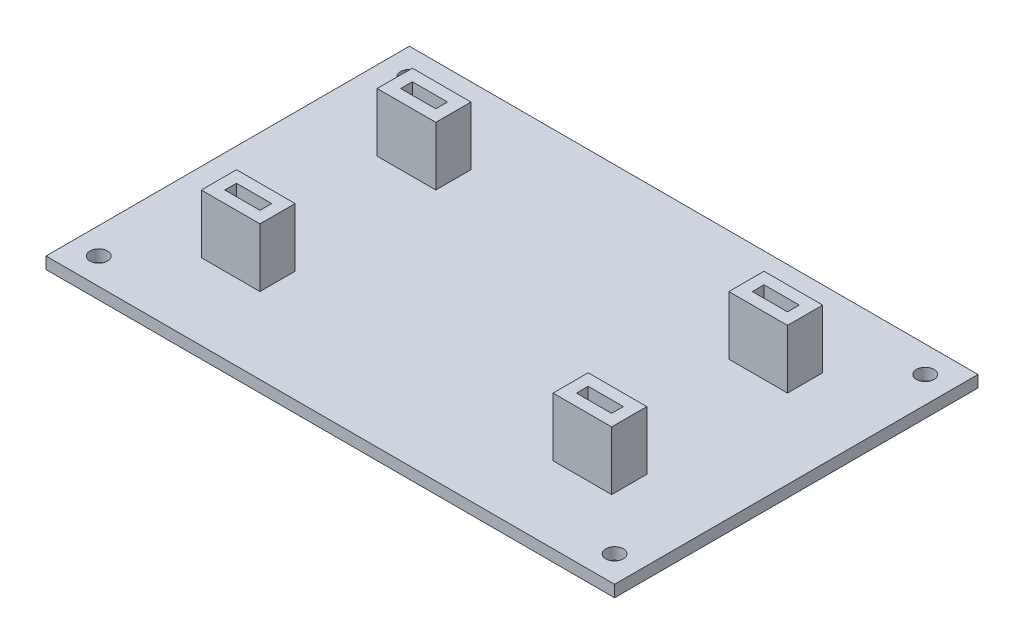
SolidWorks part; units mm, degrees
ref_plane "前视基准面" through (0, 0, 0) normal (0, 0, 1) x (1, 0, 0)
ref_plane "上视基准面" through (0, 0, 0) normal (0, 1, 0) x (1, 0, 0)
ref_plane "右视基准面" through (0, 0, 0) normal (1, 0, 0) x (0, 0, -1)
sketch "草图1" plane through (0, 0, 0) normal (0, 1, 0) x (1, 0, 0)
  line L1 (-48.5, 31) -> (48.5, 31)
  line L2 (-48.5, 31) -> (-48.5, -31)
  line L3 (-48.5, -31) -> (48.5, -31)
  line L4 (48.5, 31) -> (48.5, -31)
  line L5 (-48.5, 31) -> (48.5, -31) construction
  line L6 (-48.5, -31) -> (48.5, 31) construction
  point P0 (0, 0)
  dimension "D1" = 62
  dimension "D2" = 97
extrude "底板" add sketch "草图1" along normal blind 2
sketch "草图2" plane through (0, 2, 0) normal (0, 1, 0) x (1, 0, 0)
  line L1 (-44, 26.5) -> (44, 26.5)
  line L2 (-44, 26.5) -> (-44, -26.5)
  line L3 (-44, -26.5) -> (44, -26.5)
  line L4 (44, 26.5) -> (44, -26.5)
  line L5 (-44, 26.5) -> (44, -26.5) construction
  line L6 (-44, -26.5) -> (44, 26.5) construction
  circle A0 centre (-44, 26.5) radius 1.5
  circle A1 centre (44, 26.5) radius 1.5
  circle A2 centre (-44, -26.5) radius 1.5
  circle A3 centre (44, -26.5) radius 1.5
  point P0 (0, 0)
  dimension "D3" = 3
  dimension "D4" = 3
  dimension "D5" = 3
  dimension "D6" = 3
  dimension "D1" = 53
  dimension "D2" = 88
extrude "螺丝孔" cut sketch "草图2" against normal blind 2 contours A0 | A2 | A3 | A1
sketch "草图3" plane through (0, 2, 0) normal (0, 1, 0) x (1, 0, 0)
  line L1 (30, 15) -> (-30, 15)
  line L2 (30, 15) -> (30, -15)
  line L3 (30, -15) -> (-30, -15)
  line L4 (-30, 15) -> (-30, -15)
  line L5 (30, 15) -> (-30, -15) construction
  line L6 (30, -15) -> (-30, 15) construction
  line L7 (-27, 16) -> (-33, 16)
  line L8 (-27, 16) -> (-27, 14)
  line L9 (-27, 14) -> (-33, 14)
  line L10 (-33, 16) -> (-33, 14)
  line L11 (-27, 16) -> (-33, 14) construction
  line L12 (-27, 14) -> (-33, 16) construction
  line L13 (-25, 18) -> (-35, 18)
  line L14 (-25, 18) -> (-25, 12)
  line L15 (-25, 12) -> (-35, 12)
  line L16 (-35, 18) -> (-35, 12)
  line L17 (-25, 18) -> (-35, 12) construction
  line L18 (-25, 12) -> (-35, 18) construction
  line L19 (-25, -18) -> (-35, -18)
  line L20 (-25, -18) -> (-25, -12)
  line L21 (-25, -12) -> (-35, -12)
  line L22 (-35, -18) -> (-35, -12)
  line L23 (-25, -18) -> (-35, -12) construction
  line L24 (-25, -12) -> (-35, -18) construction
  line L25 (-27, -16) -> (-33, -16)
  line L26 (-27, -16) -> (-27, -14)
  line L27 (-27, -14) -> (-33, -14)
  line L28 (-33, -16) -> (-33, -14)
  line L29 (-27, -16) -> (-33, -14) construction
  line L30 (-27, -14) -> (-33, -16) construction
  line L31 (25, -12) -> (35, -12)
  line L32 (25, -12) -> (25, -18)
  line L33 (25, -18) -> (35, -18)
  line L34 (35, -12) -> (35, -18)
  line L35 (25, -12) -> (35, -18) construction
  line L36 (25, -18) -> (35, -12) construction
  line L37 (27, -16) -> (33, -16)
  line L38 (27, -16) -> (27, -14)
  line L39 (27, -14) -> (33, -14)
  line L40 (33, -16) -> (33, -14)
  line L41 (27, -16) -> (33, -14) construction
  line L42 (27, -14) -> (33, -16) construction
  line L43 (25, 18) -> (35, 18)
  line L44 (25, 18) -> (25, 12)
  line L45 (25, 12) -> (35, 12)
  line L46 (35, 18) -> (35, 12)
  line L47 (25, 18) -> (35, 12) construction
  line L48 (25, 12) -> (35, 18) construction
  line L49 (27, 14) -> (33, 14)
  line L50 (27, 14) -> (27, 16)
  line L51 (27, 16) -> (33, 16)
  line L52 (33, 14) -> (33, 16)
  line L53 (27, 14) -> (33, 16) construction
  line L54 (27, 16) -> (33, 14) construction
  point P0 (0, 0)
  dimension "D1" = 60
  dimension "D2" = 30
  dimension "D3" = 2
  dimension "D4" = 6
  dimension "D5" = 10
  dimension "D6" = 6
  dimension "D7" = 10
  dimension "D8" = 6
  dimension "D9" = 2
  dimension "D10" = 6
  dimension "D11" = 2
  dimension "D12" = 6
  dimension "D13" = 10
  dimension "D14" = 6
  dimension "D15" = 2
  dimension "D16" = 6
  dimension "D17" = 10
  dimension "D18" = 6
extrude "连接口" add sketch "草图3" along normal blind 10 contours L13 L16 L15 L4 L9 L10 L7 L8 L1 L14 | L15 L14 L1 L8 L9 L4 | L25 L28 L27 L4 L21 L22 L19 L20 L3 L26 | L27 L26 L3 L20 L21 L4 | L40 L37 L38 L3 L32 L33 L34 L31 L2 L39 | L38 L39 L2 L31 L32 L3 | L52 L49 L2 L45 L46 L43 L44 L1 L50 L51 | L49 L50 L1 L44 L45 L2 region at (27.25, 2, -13.25) region at (26, 2, -15.1166) region at (-27.25, 2, -13.25) region at (-26, 2, -15.1166) region at (32.5, 2, 12.1166) region at (27.25, 2, 13.25) region at (-27.25, 2, 13.25) region at (-30.1166, 2, 13)
